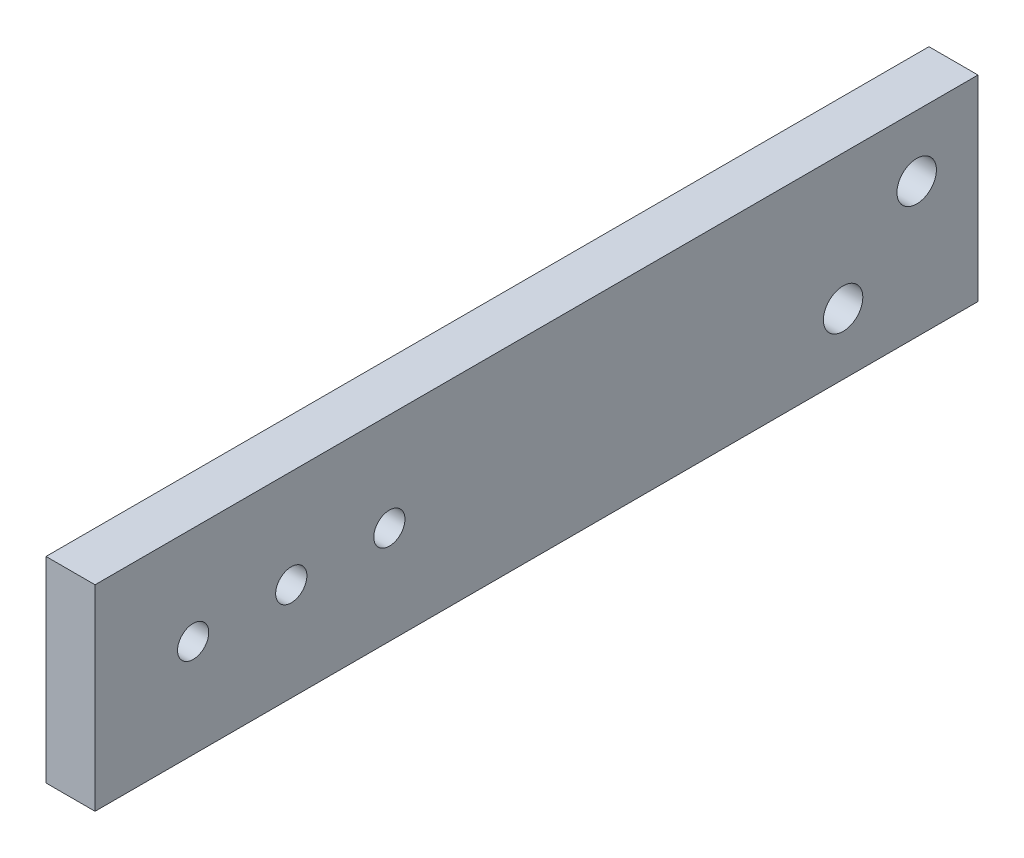
SolidWorks part; units mm, degrees
material "6061-T6 (SS)"
ref_plane "Front" through (0, 0, 0) normal (0, 0, 1) x (1, 0, 0)
ref_plane "Top" through (0, 0, 0) normal (0, 1, 0) x (1, 0, 0)
ref_plane "Right" through (0, 0, 0) normal (1, 0, 0) x (0, 0, -1)
sketch "Sketch1" plane through (0, 0, 0) normal (1, 0, 0) x (0, 0, -1)
  line L1 (0, 0) -> (114.3, 0)
  line L2 (0, 0) -> (0, 25.4)
  line L3 (0, 25.4) -> (114.3, 25.4)
  line L6 (114.3, 25.4) -> (114.3, 0)
  dimension "D1" = 25.4
  dimension "D2" = 114.3
extrude "Boss-Extrude1" add sketch "Sketch1" along normal blind 6.35
hole_wizard "#10-32 Tapped Hole1" positions "Sketch2" profile "Sketch3" tap size "#10-32" standard "ANSI Inch" end condition through all
sketch "Sketch2" plane through (6.35, 0, 0) normal (1, 0, 0) x (0, 0, -1)
  line L0 (0, 0) -> (12.7, 12.7) construction
  line L1 (12.7, 12.7) -> (25.4, 12.7) construction
  line L2 (25.4, 12.7) -> (38.1, 12.7) construction
  line L3 (38.1, 12.7) -> (50.8, 25.4) construction
  line L4 (114.3, 25.4) -> (0, 25.4) construction
  line L6 (0, 25.4) -> (0, 0) construction
  point P0 (12.7, 12.7)
  point P2 (25.4, 12.7)
  point P4 (38.1, 12.7)
  point P20 (0, 0)
  dimension "D1" = 50.8
  dimension "D2" = 12.7
sketch "Sketch3" plane through (6.35, 12.7, -12.7) normal (0, 1, 0) x (0, 0, -1)
  line L0 (0, 0) -> (0, 6.35)
  line L1 (0, 6.35) -> (2.0193, 6.35)
  line L2 (2.0193, 6.35) -> (2.0193, 0)
  line L5 (2.0193, 0) -> (0, 0)
  line L11 (0, -6.35) -> (0, 107.95) construction
  dimension "Thru Tap Drill Dia." = 4.0386
  dimension "Thru Tap Drill Depth" = 6.35
cosmetic thread "Hole Thread1"
cosmetic thread "Hole Thread2"
cosmetic thread "Hole Thread3"
hole_wizard "#10 Clearance Hole1" positions "Sketch4" profile "Sketch5" hole size "#10" standard "ANSI Inch" end condition through all
sketch "Sketch4" plane through (6.35, 0, 0) normal (1, 0, 0) x (0, 0, -1)
  line L0 (88.9, 0) -> (96.8375, 7.9375) construction
  line L1 (0, 0) -> (114.3, 0) construction
  line L2 (96.8375, 7.9375) -> (106.3625, 17.4625) construction
  line L3 (106.3625, 17.4625) -> (114.3, 25.4) construction
  line L5 (114.3, 0) -> (114.3, 25.4) construction
  point P13 (106.3625, 17.4625)
  point P15 (96.8375, 7.9375)
  dimension "D1" = 25.4
  dimension "D2" = 9.525
sketch "Sketch5" plane through (6.35, 17.4625, -106.3625) normal (0, 1, 0) x (0, 0, -1)
  line L0 (0, 0) -> (0, 6.35)
  line L1 (0, 6.35) -> (2.5527, 6.35)
  line L2 (2.5527, 6.35) -> (2.5527, 0)
  line L5 (2.5527, 0) -> (0, 0)
  line L11 (0, -6.35) -> (0, 107.95) construction
  dimension "Thru Hole Dia." = 5.1054
  dimension "Thru Hole Depth" = 6.35
